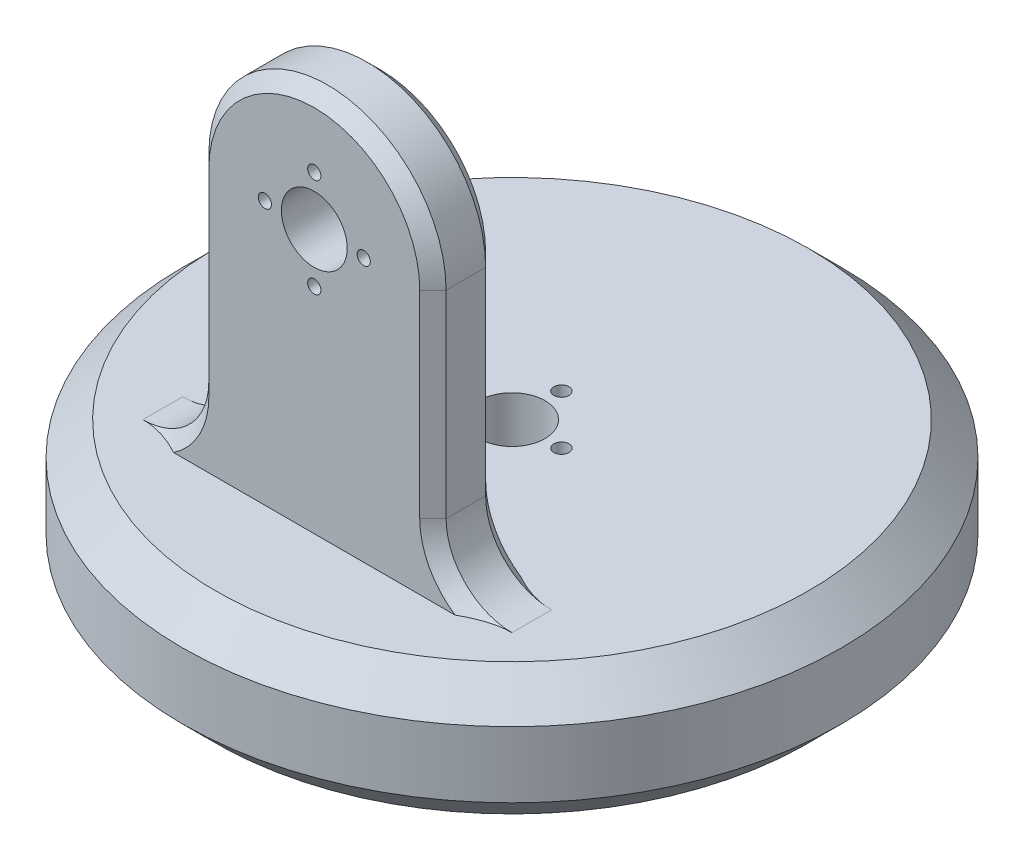
SolidWorks part; units mm, degrees
ref_plane "Front Plane" through (0, 0, 0) normal (0, 0, 1) x (1, 0, 0)
ref_plane "Top Plane" through (0, 0, 0) normal (0, 1, 0) x (1, 0, 0)
ref_plane "Right Plane" through (0, 0, 0) normal (1, 0, 0) x (0, 0, -1)
ref_axis "Axis1" through (0, -3.9, 0) along (0, 1, 0)
sketch "Sketch1" plane through (0, 0, 0) normal (0, 0, 1) x (1, 0, 0)
  line L0 (45, 0) -> (50, 5)
  line L1 (50, 5) -> (50, 15)
  line L2 (50, 15) -> (45, 20)
  line L3 (45, 20) -> (5, 20)
  line L4 (5, 20) -> (5, 0)
  line L5 (5, 0) -> (45, 0)
  line L6 (7, 18) -> (7, 2) construction
  line L7 (9, 2) -> (44.1716, 2)
  line L8 (44.1716, 2) -> (48, 5.8284)
  line L9 (48, 5.8284) -> (48, 14.1716)
  line L10 (48, 14.1716) -> (44.1716, 18)
  line L11 (44.1716, 18) -> (9, 18)
  line L12 (9, 18) -> (9, 2)
  line L13 (7, 2) -> (44.1716, 2) construction
  line L14 (44.1716, 18) -> (7, 18) construction
  dimension "D1" = 5
  dimension "D2" = 5
  dimension "D3" = 10
  dimension "D4" = 45
  dimension "D5" = 2
  dimension "D6" = 4
  dimension "D7" = 5
revolve "Revolve1" add sketch "Sketch1" angle 360 about axis through (0, -3.9, 0) along (0, 1, 0)
sketch "Sketch2" plane through (0, 0, 0) normal (0, -1, 0) x (1, 0, 0)
  circle A0 centre (0, 0) radius 7.5 construction
  circle A1 centre (7.5, 0) radius 1.15
  circle A2 centre (0, 7.5) radius 1.15
  circle A3 centre (-7.5, 0) radius 1.15
  circle A4 centre (0, -7.5) radius 1.15
  circle A5 centre (0, 0) radius 5
  dimension "D1" = 15
  dimension "D2" = 2.3
  dimension "D3" = 10
extrude "Cut-Extrude1" cut sketch "Sketch2" against normal through all
sketch "Sketch6" plane through (0, 0, 0) normal (0, 0, 1) x (1, 0, 0)
  line L7 (45, 20) -> (-45, 20) construction
  line L8 (18, 60) -> (18, 20)
  line L9 (-18, 20) -> (18, 20)
  line L22 (-18, 60) -> (-18, 20)
  arc A18 (-18, 60) -> (18, 60) centre (0, 60) cw
  circle A19 centre (0, 60) radius 5
  circle A26 centre (0, 60) radius 7.5 construction
  circle A27 centre (0, 52.5) radius 1
  circle A28 centre (7.5, 60) radius 1
  circle A29 centre (0, 67.5) radius 1
  circle A30 centre (-7.5, 60) radius 1
  dimension "D1" = 10
  dimension "D3" = 15
  dimension "D4" = 40
  dimension "D5" = 36
  dimension "D2" = 2
extrude "Boss-Extrude1" add sketch "Sketch6" along normal blind 10 from offset 20
fillet "Fillet1" radius 10 2 edges at (18, 20, 25) (-18, 20, 25)
chamfer "Chamfer1" distance 2 angle 45 10 edges at (-20.9289, 22.9289, 20) (-18, 45, 20) (20.9289, 22.9289, 20) (0, 78, 20) (18, 45, 20) (-20.9289, 22.9289, 30) (-18, 45, 30) (20.9289, 22.9289, 30) (0, 78, 30) (18, 45, 30)
